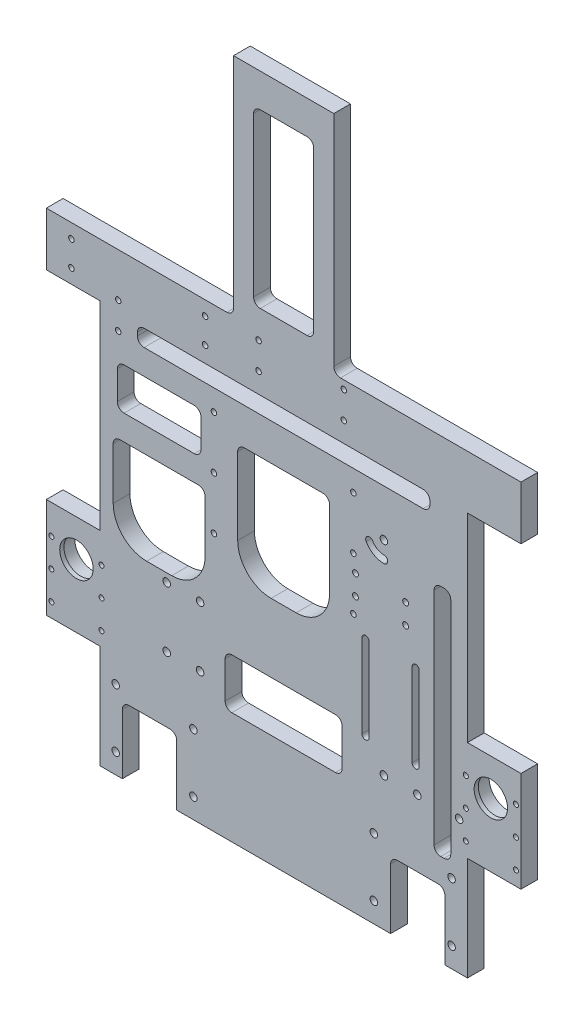
SolidWorks part; units mm, degrees
ref_plane "Front" through (0, 0, 0) normal (0, 0, 1) x (1, 0, 0)
ref_plane "Top" through (0, 0, 0) normal (0, 1, 0) x (1, 0, 0)
ref_plane "Right" through (0, 0, 0) normal (1, 0, 0) x (0, 0, -1)
sketch "Esquisse1" plane through (0, 0, 0) normal (0, 0, 1) x (1, 0, 0)
  line L1 (0, 0) -> (220, 0)
  line L2 (0, 0) -> (0, 285)
  line L3 (0, 285) -> (220, 285)
  line L4 (220, 0) -> (220, 285)
  dimension "D1" = 220
  dimension "D2" = 285
extrude "Boss.-Extru.1" add sketch "Esquisse1" along normal blind 10
sketch "Esquisse2" plane through (0, 0, 0) normal (0, -1, 0) x (1, 0, 0)
  line L0 (0, 5) -> (220, 5) construction
  line L1 (0, 10) -> (0, 0) construction
  line L2 (220, 10) -> (220, 0) construction
  line L3 (110, 5) -> (110, 28.0559) construction
  circle A0 centre (110, 5) radius 2
  circle A1 centre (213, 5) radius 2
  circle A2 centre (7, 5) radius 2
  dimension "D1" = 4
  dimension "D2" = 103
extrude "Enlèv. mat.-Extru.1" cut sketch "Esquisse2" against normal blind 8
sketch "Esquisse3" plane through (0, 0, 10) normal (0, 0, 1) x (1, 0, 0)
  line L0 (110, 0) -> (110, 285) construction
  line L1 (0, 0) -> (220, 0) construction
  line L2 (220, 285) -> (0, 285) construction
  line L3 (82.5, 208) -> (137.5, 208)
  line L4 (137.5, 208) -> (137.5, 138)
  line L5 (137.5, 138) -> (82.5, 138)
  line L6 (82.5, 208) -> (82.5, 138)
  line L8 (8, 175) -> (63, 175)
  line L9 (8, 175) -> (8, 120)
  line L10 (8, 120) -> (63, 120)
  line L11 (63, 175) -> (63, 120)
  line L12 (200, 55) -> (210, 55)
  line L13 (200, 55) -> (200, 195)
  line L14 (200, 195) -> (210, 195)
  line L15 (210, 55) -> (210, 195)
  point P11 (110, 138)
  point P12 (110, 208)
  dimension "D1" = 70
  dimension "D2" = 55
  dimension "D3" = 138
  dimension "D4" = 55
  dimension "D5" = 47
  dimension "D6" = 55
  dimension "D7" = 120
  dimension "D8" = 140
  dimension "D9" = 55
  dimension "D10" = 90
  dimension "D11" = 10
extrude "Enlèv. mat.-Extru.2" cut sketch "Esquisse3" against normal through all both and the other way through all
sketch "Esquisse5" plane through (0, 0, 10) normal (0, 0, 1) x (1, 0, 0)
  line L0 (110, 230) -> (110, 0) construction
  line L1 (22.5, 240) -> (197.5, 240)
  line L2 (22.5, 240) -> (22.5, 230)
  line L3 (22.5, 230) -> (197.5, 230)
  line L4 (197.5, 240) -> (197.5, 230)
  line L5 (0, 0) -> (220, 0) construction
  dimension "D1" = 175
  dimension "D2" = 10
  dimension "D3" = 230
extrude "Enlèv. mat.-Extru.3" cut sketch "Esquisse5" against normal through all both and the other way through all
sketch "Esquisse6" plane through (0, 0, 10) normal (0, 0, 1) x (1, 0, 0)
  line L0 (170, 80) -> (190, 80) construction
  line L1 (0, 0) -> (220, 0) construction
  line L2 (137.5, 138) -> (82.5, 138) construction
  line L3 (215, 80) -> (190, 80) construction
  line L4 (168, 193.9299) -> (168, 170.25) construction
  line L5 (186.4274, 170.25) -> (149.5726, 170.25) construction
  line L6 (0, 285) -> (0, 0) construction
  circle A0 centre (190, 80) radius 2.25
  circle A1 centre (170, 80) radius 2.25
  circle A2 centre (215, 80) radius 2.25
  circle A3 centre (153, 176.25) radius 1.75
  circle A4 centre (183, 176.25) radius 1.75
  circle A5 centre (183, 164.25) radius 1.75
  circle A6 centre (153, 164.25) radius 1.75
  point P8 (110, 138)
  dimension "D1" = 4.5
  dimension "D3" = 80
  dimension "D6" = 30
  dimension "D7" = 12
  dimension "D8" = 3.5
  dimension "D2" = 20
  dimension "D4" = 60
  dimension "D5" = 25
  dimension "D9" = 168
  dimension "D10" = 170.25
extrude "Enlèv. mat.-Extru.4" cut sketch "Esquisse6" against normal through all both and the other way through all
sketch "Esquisse7" plane through (0, 0, 10) normal (0, 0, 1) x (1, 0, 0)
  line L0 (110, 0) -> (110, 285) construction
  line L1 (0, 0) -> (220, 0) construction
  line L2 (220, 285) -> (0, 285) construction
  line L3 (68.285, 186) -> (68.285, 217.4) construction
  line L4 (68.285, 186) -> (110, 186) construction
  line L5 (151.715, 186) -> (151.715, 217.4) construction
  line L6 (95, 268) -> (120.5, 268) construction
  line L7 (120.5, 268) -> (120.5, 260) construction
  line L8 (120.5, 260) -> (137.9818, 260) construction
  line L9 (95, 252) -> (120.5, 252) construction
  line L10 (22.5, 240) -> (197.5, 240) construction
  circle A0 centre (68.285, 217.4) radius 1.65
  circle A1 centre (68.285, 186) radius 1.65
  circle A2 centre (68.285, 154.6) radius 1.65
  circle A3 centre (151.715, 154.6) radius 1.65
  circle A4 centre (151.715, 186) radius 1.65
  circle A5 centre (151.715, 217.4) radius 1.65
  circle A6 centre (95, 268) radius 1.65
  circle A7 centre (146, 268) radius 1.65
  circle A8 centre (146, 252) radius 1.65
  circle A9 centre (95, 252) radius 1.65
  dimension "D1" = 31.4
  dimension "D2" = 3.3
  dimension "D5" = 16
  dimension "D6" = 51
  dimension "D9" = 3.3
  dimension "D7" = 15
  dimension "D3" = 83.43
  dimension "D4" = 186
  dimension "D8" = 20
extrude "Enlèv. mat.-Extru.5" cut sketch "Esquisse7" against normal through all both and the other way through all
sketch "Esquisse8" plane through (0, 0, 10) normal (0, 0, 1) x (1, 0, 0)
  line L0 (110, 0) -> (110, 285) construction
  line L1 (0, 0) -> (220, 0) construction
  line L2 (220, 285) -> (0, 285) construction
  line L3 (174, 0) -> (174, 40)
  line L4 (13.5, 0) -> (46, 0)
  line L5 (13.5, 0) -> (13.5, 40)
  line L6 (13.5, 40) -> (46, 40)
  line L7 (46, 0) -> (46, 40)
  line L8 (206.5, 40) -> (174, 40)
  line L9 (206.5, 0) -> (206.5, 40)
  line L10 (206.5, 0) -> (174, 0)
  dimension "D1" = 128
  dimension "D2" = 32.5
  dimension "D3" = 40
extrude "Enlèv. mat.-Extru.6" cut sketch "Esquisse8" against normal through all both and the other way through all
fillet "Congé1" radius 20 4 edges at (137.5, 138, 5) (82.5, 138, 5) (63, 120, 5) (8, 120, 5)
sketch "Esquisse9" plane through (0, 0, 10) normal (0, 0, 1) x (1, 0, 0)
  line L0 (189, 145) -> (189, 95) construction
  line L1 (191.1, 145) -> (191.1, 95)
  line L2 (186.9, 145) -> (186.9, 95)
  line L3 (189, 120) -> (159, 120) construction
  line L4 (174, 120) -> (174, 121.5076) construction
  line L5 (159, 95) -> (159, 145) construction
  line L6 (156.9, 95) -> (156.9, 145)
  line L7 (161.1, 95) -> (161.1, 145)
  line L9 (210, 55) -> (200, 55) construction
  line L10 (200, 55) -> (200, 195) construction
  arc A0 (191.1, 145) -> (186.9, 145) centre (189, 145) ccw
  arc A1 (186.9, 95) -> (191.1, 95) centre (189, 95) ccw
  arc A2 (156.9, 95) -> (161.1, 95) centre (159, 95) ccw
  arc A3 (161.1, 145) -> (156.9, 145) centre (159, 145) ccw
  point P2 (189, 120)
  point P13 (159, 120)
  dimension "D1" = 4.2
  dimension "D2" = 30
  dimension "D3" = 11
  dimension "D4" = 40
  dimension "D5" = 50
extrude "Enlèv. mat.-Extru.7" cut sketch "Esquisse9" against normal through all both and the other way through all
sketch "Esquisse10" plane through (0, 0, 10) normal (0, 0, 1) x (1, 0, 0)
  line L0 (9.5, 0) -> (9.5, 52.9697) construction
  line L1 (0, 0) -> (13.5, 0) construction
  line L2 (0, 285) -> (0, 0) construction
  line L3 (110, 0) -> (110, 48.9194) construction
  line L4 (46, 0) -> (174, 0) construction
  line L5 (32.75, 0) -> (32.75, 52.9697) construction
  circle A0 centre (9.5, 12) radius 2.25
  circle A1 centre (9.5, 47) radius 2.25
  circle A2 centre (210.5, 47) radius 2.25
  circle A3 centre (210.5, 12) radius 2.25
  circle A4 centre (56, 47) radius 2.25
  circle A5 centre (56, 12) radius 2.25
  circle A6 centre (164, 12) radius 2.25
  circle A7 centre (164, 47) radius 2.25
  dimension "D2" = 4.5
  dimension "D3" = 35
  dimension "D4" = 12
  dimension "D5" = 46.5
  dimension "D1" = 9.5
extrude "Enlèv. mat.-Extru.8" cut sketch "Esquisse10" against normal through all both and the other way through all
sketch "Esquisse11" plane through (0, 0, 10) normal (0, 0, 1) x (1, 0, 0)
  line L0 (110, 67) -> (110, 0) construction
  line L1 (75, 97) -> (145, 97)
  line L2 (75, 97) -> (75, 67)
  line L3 (75, 67) -> (145, 67)
  line L4 (145, 97) -> (145, 67)
  line L5 (46, 0) -> (174, 0) construction
  dimension "D1" = 70
  dimension "D2" = 30
  dimension "D3" = 67
extrude "Enlèv. mat.-Extru.9" cut sketch "Esquisse11" against normal through all both and the other way through all
sketch "Esquisse12" plane through (0, 0, 10) normal (0, 0, 1) x (1, 0, 0)
  line L0 (220, 0) -> (220, 285) construction
  line L1 (46, 0) -> (174, 0) construction
  line L2 (170, 202) -> (161.3397, 197) construction
  line L3 (170, 192) -> (170, 202) construction
  circle A0 centre (170, 202) radius 2.25
  arc A1 (161.3397, 197) -> (170, 192) centre (170, 202) ccw construction
  arc A2 (159.3912, 195.875) -> (170, 189.75) centre (170, 202) ccw
  arc A3 (163.2883, 198.125) -> (170, 194.25) centre (170, 202) ccw
  arc A4 (163.2883, 198.125) -> (159.3912, 195.875) centre (161.3397, 197) ccw
  arc A5 (170, 189.75) -> (170, 194.25) centre (170, 192) ccw
  point P9 (165, 193.3397)
  dimension "D1" = 4.5
  dimension "D2" = 50
  dimension "D3" = 202
  dimension "D4" = 4.5
  dimension "D5" = 10
  dimension "D6" = 60
extrude "Enlèv. mat.-Extru.10" cut sketch "Esquisse12" against normal through all both and the other way through all
sketch "Esquisse13" plane through (0, 0, 10) normal (0, 0, 1) x (1, 0, 0)
  line L0 (50, 123.132) -> (50, 97) construction
  line L1 (50, 97) -> (30.3926, 97) construction
  line L2 (46, 0) -> (174, 0) construction
  line L3 (0, 285) -> (0, 0) construction
  circle A0 centre (40, 115) radius 2.25
  circle A1 centre (60, 115) radius 2.25
  circle A2 centre (60, 79) radius 2.25
  circle A3 centre (40, 79) radius 2.25
  dimension "D1" = 36
  dimension "D2" = 20
  dimension "D3" = 4.5
  dimension "D4" = 97
  dimension "D5" = 40
extrude "Enlèv. mat.-Extru.11" cut sketch "Esquisse13" against normal through all both and the other way through all
sketch "Esquisse14" plane through (0, 0, 10) normal (0, 0, 1) x (1, 0, 0)
  line L0 (110, 0) -> (110, 159.9943) construction
  line L1 (0, 285) -> (80, 285)
  line L2 (0, 285) -> (0, 273)
  line L3 (0, 273) -> (80, 273)
  line L4 (80, 285) -> (80, 273)
  line L5 (46, 0) -> (174, 0) construction
  line L6 (140, 285) -> (140, 273)
  line L7 (220, 273) -> (140, 273)
  line L8 (220, 285) -> (220, 273)
  line L9 (220, 285) -> (140, 285)
  dimension "D1" = 12
  dimension "D2" = 80
extrude "Enlèv. mat.-Extru.12" cut sketch "Esquisse14" against normal through all both and the other way through all
sketch "Esquisse15" plane through (0, 0, 10) normal (0, 0, 1) x (1, 0, 0)
  line L0 (140, 285) -> (80, 285) construction
  line L1 (80, 285) -> (140, 285)
  line L2 (80, 285) -> (80, 408)
  line L3 (80, 408) -> (140, 408)
  line L4 (140, 285) -> (140, 408)
  line L5 (110, 408) -> (110, 0) construction
  line L6 (46, 0) -> (174, 0) construction
  dimension "D1" = 60
  dimension "D2" = 123
extrude "Boss.-Extru.2" add sketch "Esquisse15" against normal up to vertex (10 mm away) up to point (13.5, 0, 0)
sketch "Esquisse16" plane through (0, 0, 10) normal (0, 0, 1) x (1, 0, 0)
  line L0 (110, 388) -> (110, 408) construction
  line L1 (92, 285) -> (128, 285)
  line L2 (92, 285) -> (92, 388)
  line L3 (92, 388) -> (128, 388)
  line L4 (128, 285) -> (128, 388)
  line L5 (140, 408) -> (80, 408) construction
  line L6 (140, 273) -> (140, 408) construction
  line L7 (80, 273) -> (0, 273) construction
  dimension "D1" = 12
  dimension "D2" = 20
  dimension "D3" = 12
extrude "Enlèv. mat.-Extru.13" cut sketch "Esquisse16" against normal through all both and the other way through all
sketch "Esquisse17" plane through (0, 0, 10) normal (0, 0, 1) x (1, 0, 0)
  line L0 (110, 0) -> (110, -39.2027) construction
  line L1 (220, 273) -> (252, 273)
  line L2 (220, 273) -> (220, 241)
  line L3 (220, 241) -> (252, 241)
  line L4 (252, 273) -> (252, 241)
  line L5 (46, 0) -> (174, 0) construction
  line L6 (-32, 273) -> (-32, 241)
  line L7 (0, 241) -> (-32, 241)
  line L8 (0, 273) -> (0, 241)
  line L9 (0, 273) -> (-32, 273)
  line L10 (0, 273) -> (0, 0) construction
  line L11 (0, 62) -> (-32, 62)
  line L12 (0, 62) -> (0, 122)
  line L13 (0, 122) -> (-32, 122)
  line L14 (-32, 62) -> (-32, 122)
  line L15 (252, 62) -> (252, 122)
  line L16 (220, 122) -> (252, 122)
  line L17 (220, 62) -> (220, 122)
  line L18 (220, 62) -> (252, 62)
  dimension "D1" = 32
  dimension "D2" = 32
  dimension "D3" = 60
  dimension "D4" = 62
extrude "Boss.-Extru.3" add sketch "Esquisse17" against normal up to vertex (10 mm away) up to point (140, 273, 0)
sketch "Esquisse18" plane through (0, 0, 10) normal (0, 0, 1) x (1, 0, 0)
  line L0 (35.5, 190) -> (35.5, 175) construction
  line L1 (10.5, 190) -> (60.5, 190)
  line L2 (10.5, 190) -> (10.5, 215)
  line L3 (10.5, 215) -> (60.5, 215)
  line L4 (60.5, 190) -> (60.5, 215)
  line L5 (8, 175) -> (63, 175) construction
  dimension "D1" = 25
  dimension "D2" = 50
  dimension "D3" = 15
extrude "Enlèv. mat.-Extru.14" cut sketch "Esquisse18" against normal through all both and the other way through all
fillet "Congé2" radius 4 30 edges at (137.5, 208, 5) (82.5, 208, 5) (197.5, 230, 5) (197.5, 240, 5) (22.5, 240, 5) (22.5, 230, 5) (63, 175, 5) (8, 175, 5) (200, 195, 5) (210, 195, 5) (210, 55, 5) (200, 55, 5) (206.5, 40, 5) (174, 40, 5) (46, 40, 5) (13.5, 40, 5) (75, 67, 5) (145, 67, 5) (145, 97, 5) (75, 97, 5) (92, 388, 5) (128, 388, 5) (128, 285, 5) (92, 285, 5) (140, 273, 5) (80, 273, 5) (10.5, 215, 5) (60.5, 215, 5) (60.5, 190, 5) (10.5, 190, 5)
sketch "Esquisse19" plane through (0, 0, 10) normal (0, 0, 1) x (1, 0, 0)
  line L0 (-32, 257) -> (54.3473, 257) construction
  line L1 (-32, 273) -> (-32, 241) construction
  line L2 (23, 257) -> (23, 269.1) construction
  line L3 (11, 230.8) -> (11, 246.8) construction
  circle A0 centre (-17, 264.5) radius 1.65
  circle A1 centre (-17, 249.5) radius 1.65
  circle A2 centre (63, 249.5) radius 1.65
  circle A3 centre (63, 264.5) radius 1.65
  circle A4 centre (11, 246.8) radius 1.65
  circle A5 centre (11, 230.8) radius 1.65
  dimension "D2" = 80
  dimension "D3" = 3.3
  dimension "D5" = 28
  dimension "D6" = 16
  dimension "D7" = 10.2
  dimension "D1" = 15
  dimension "D4" = 55
extrude "Enlèv. mat.-Extru.15" cut sketch "Esquisse19" against normal through all both and the other way through all
sketch "Esquisse20" plane through (0, 0, 0) normal (0, 0, 1) x (1, 0, 0)
  line L0 (-32, 100) -> (-14, 100) construction
  line L2 (110, 0) -> (110, 74.504) construction
  line L3 (46, 0) -> (174, 0) construction
  line L4 (252, 100) -> (234, 100) construction
  line L5 (-32, 122) -> (-32, 62) construction
  circle A0 centre (-14, 100) radius 11.025
  circle A1 centre (234, 100) radius 11.025
  point P2 (-32, 90)
  point P12 (0, 0)
  dimension "D1" = 22.05
  dimension "D3" = 100
  dimension "D2" = 18
extrude "Enlèv. mat.-Extru.16" cut sketch "Esquisse20" along normal blind 7.5
sketch "Esquisse21" plane through (0, 0, 7.5) normal (0, 0, -1) x (-1, 0, 0)
  line L0 (-110, 0) -> (-110, 78) construction
  line L1 (-46, 0) -> (-174, 0) construction
  circle A0 centre (14, 100) radius 10
  circle A1 centre (-234, 100) radius 10
  dimension "D1" = 20
extrude "Enlèv. mat.-Extru.17" cut sketch "Esquisse21" against normal through all both and the other way through all
sketch "Esquisse22" plane through (0, 0, 10) normal (0, 0, 1) x (1, 0, 0)
  line L0 (-14, 104.5) -> (-14, 70.5) construction
  line L1 (-14, 70.5) -> (-29, 70.5) construction
  line L2 (-14, 87.5) -> (-29, 87.5) construction
  line L3 (-14, 104.5) -> (-14, 110) construction
  line L4 (-29, 70.5) -> (-29, 87.5) construction
  line L5 (-14, 110) -> (-4, 100) construction
  line L6 (-24, 100) -> (-14, 110) construction
  line L7 (-24, 100) -> (-4, 100) construction
  line L8 (110, 0) -> (110, 176.4772) construction
  line L9 (46, 0) -> (174, 0) construction
  line L10 (244, 100) -> (224, 100) construction
  line L11 (244, 100) -> (234, 110) construction
  line L12 (234, 110) -> (224, 100) construction
  line L13 (249, 70.5) -> (249, 87.5) construction
  line L14 (234, 104.5) -> (234, 110) construction
  line L15 (234, 87.5) -> (249, 87.5) construction
  line L16 (234, 70.5) -> (249, 70.5) construction
  line L17 (234, 104.5) -> (234, 70.5) construction
  circle A0 centre (-29, 70.5) radius 1.5
  circle A1 centre (-29, 87.5) radius 1.5
  circle A2 centre (-29, 104.5) radius 1.5
  circle A3 centre (1, 104.5) radius 1.5
  circle A4 centre (1, 87.5) radius 1.5
  circle A5 centre (1, 70.5) radius 1.5
  circle A7 centre (-14, 100) radius 10 construction
  circle A8 centre (219, 70.5) radius 1.5
  circle A9 centre (219, 87.5) radius 1.5
  circle A10 centre (219, 104.5) radius 1.5
  circle A11 centre (249, 104.5) radius 1.5
  circle A12 centre (249, 87.5) radius 1.5
  circle A13 centre (249, 70.5) radius 1.5
  dimension "D1" = 3
  dimension "D2" = 30
  dimension "D3" = 17
  dimension "D4" = 12.5
extrude "Enlèv. mat.-Extru.18" cut sketch "Esquisse22" against normal through all both and the other way through all
